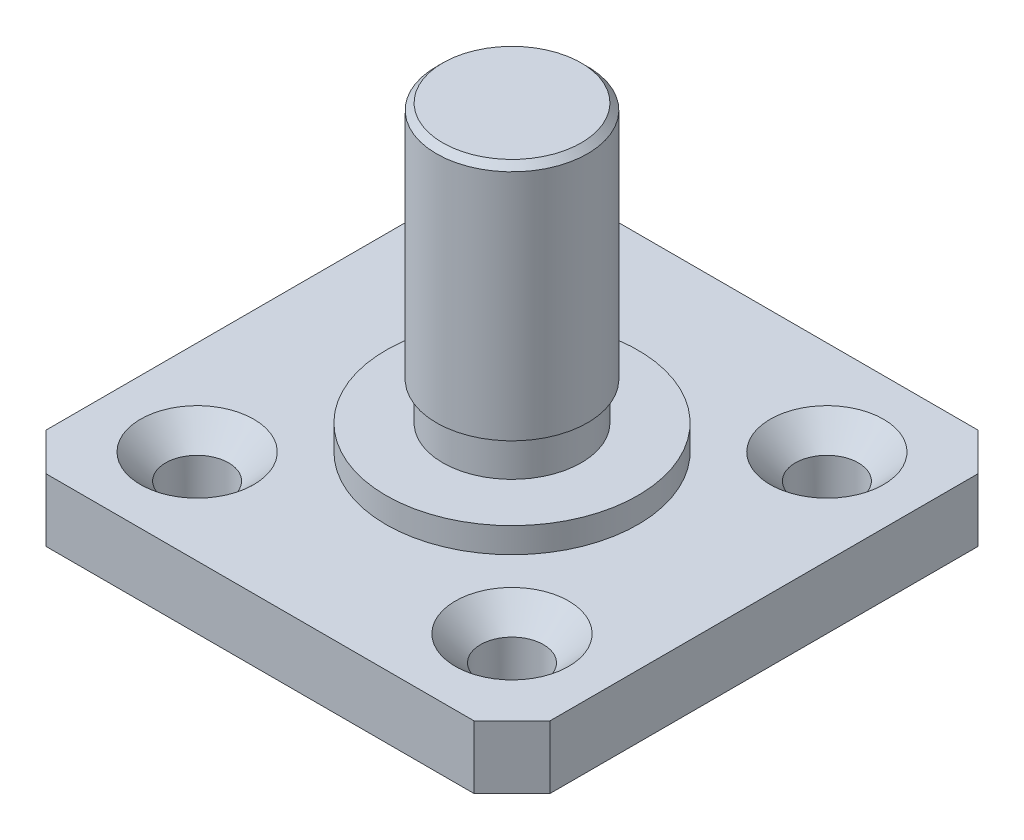
SolidWorks part; units mm, degrees
material "Литая углеродистая сталь"
ref_plane "Спереди" through (0, 0, 0) normal (0, 0, 1) x (1, 0, 0)
ref_plane "Сверху" through (0, 0, 0) normal (0, 1, 0) x (1, 0, 0)
ref_plane "Справа" through (0, 0, 0) normal (1, 0, 0) x (0, 0, -1)
sketch "Эскиз1" plane through (0, 0, 0) normal (0, 1, 0) x (1, 0, 0)
  line L1 (-20, -20) -> (20, -20)
  line L2 (-20, -20) -> (-20, 20)
  line L3 (-20, 20) -> (20, 20)
  line L4 (20, -20) -> (20, 20)
  line L5 (0, 20) -> (0, -20) construction
  line L6 (-20, 0) -> (20, 0) construction
  point P0 (0, 0)
  dimension "D1" = 40
extrude "Бобышка-Вытянуть1" add sketch "Эскиз1" along normal blind 5
chamfer "Фаска1" distance 3 angle 45 4 edges at (-20, 2.5, -20) (20, 2.5, -20) (-20, 2.5, 20) (20, 2.5, 20)
sketch "Эскиз2" plane through (0, 5, 0) normal (0, 1, 0) x (1, 0, 0)
  circle A0 centre (0, 0) radius 10
  dimension "D1" = 20
extrude "Бобышка-Вытянуть2" add sketch "Эскиз2" along normal blind 2
sketch "Эскиз3" plane through (0, 7, 0) normal (0, 1, 0) x (1, 0, 0)
  circle A0 centre (0, 0) radius 6
  dimension "D1" = 12
extrude "Бобышка-Вытянуть3" add sketch "Эскиз3" along normal blind 22
sketch "Эскиз4" plane through (0, 7, 0) normal (0, 1, 0) x (1, 0, 0)
  circle A0 centre (0, 0) radius 6 construction
  circle A1 centre (0, 0) radius 6
  circle A4 centre (0, 0) radius 5.5
  circle A5 centre (0, 0) radius 5.5
  dimension "D1" = 0.5
extrude "Вырез-Вытянуть1" cut sketch "Эскиз4" along normal blind 3
sketch "Эскиз5" plane through (0, 5, 0) normal (0, 1, 0) x (1, 0, 0)
  line L0 (0, 0) -> (0, 8.071) construction
  line L1 (0, 0) -> (4.4681, 0) construction
  circle A0 centre (-12.5, 12.5) radius 2.5
  circle A1 centre (12.5, 12.5) radius 2.5
  circle A2 centre (12.5, -12.5) radius 2.5
  circle A3 centre (-12.5, -12.5) radius 2.5
  dimension "D1" = 5
  dimension "D2" = 25
  dimension "D3" = 25
extrude "Вырез-Вытянуть2" cut sketch "Эскиз5" against normal through all
chamfer "Фаска2" distance 2 angle 45 4 edges at (-12.5, 5, 15) (12.5, 5, 15) (12.5, 5, -10) (-12.5, 5, -10)
chamfer "Фаска3" distance 0.5 angle 45 1 edges at (0, 29, 6)
